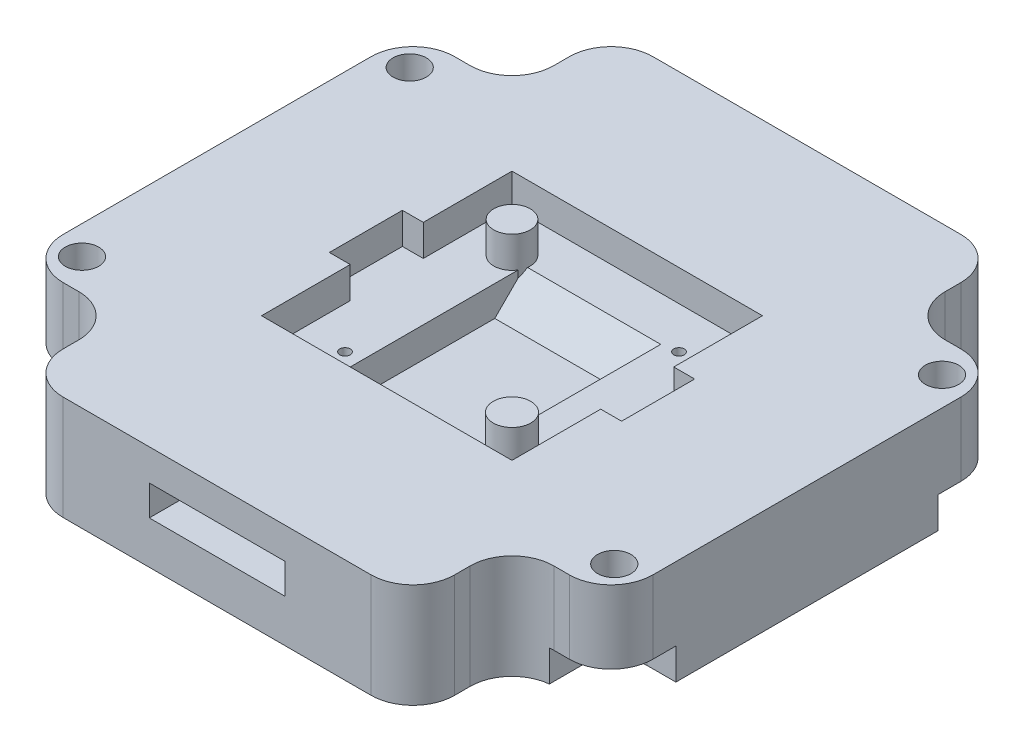
SolidWorks part; units mm, degrees
ref_plane "Ebene vorne" through (0, 0, 0) normal (0, 0, 1) x (1, 0, 0)
ref_plane "Ebene oben" through (0, 0, 0) normal (0, 1, 0) x (1, 0, 0)
ref_plane "Ebene rechts" through (0, 0, 0) normal (1, 0, 0) x (0, 0, -1)
sketch "Skizze1" plane through (0, 0, 0) normal (0, 1, 0) x (1, 0, 0)
  line L0 (18.75, 18.75) -> (28.25, 18.75)
  line L1 (-28.25, 18.75) -> (-18.75, 18.75)
  line L2 (-28.25, 18.75) -> (-28.25, -18.75)
  line L3 (-28.25, -18.75) -> (-18.75, -18.75)
  line L4 (28.25, 18.75) -> (28.25, -18.75)
  line L5 (-28.25, 18.75) -> (28.25, -18.75) construction
  line L6 (-28.25, -18.75) -> (28.25, 18.75) construction
  line L7 (-18.75, -28.25) -> (18.75, -28.25)
  line L8 (-18.75, -28.25) -> (-18.75, -18.75)
  line L9 (-18.75, 28.25) -> (18.75, 28.25)
  line L10 (18.75, -28.25) -> (18.75, -18.75)
  line L11 (-18.75, -28.25) -> (18.75, 28.25) construction
  line L12 (-18.75, 28.25) -> (18.75, -28.25) construction
  line L13 (18.75, 18.75) -> (18.75, 28.25)
  line L14 (18.75, -18.75) -> (28.25, -18.75)
  line L15 (-18.75, 18.75) -> (-18.75, 28.25)
  point P0 (0, 0)
  point P6 (0, 0)
  dimension "D1" = 56.5
  dimension "D2" = 56.5
  dimension "D3" = 37.5
extrude "Aufsatz-Linear austragen1" add sketch "Skizze1" along normal blind 10
sketch "Skizze2" plane through (0, 10, 0) normal (0, 1, 0) x (1, 0, 0)
  line L1 (-12, 12) -> (12, 12)
  line L2 (-12, 12) -> (-12, -12)
  line L3 (-12, -12) -> (12, -12)
  line L4 (12, 12) -> (12, -12)
  line L5 (-12, 12) -> (12, -12) construction
  line L6 (-12, -12) -> (12, 12) construction
  point P0 (0, 0)
  dimension "D1" = 24
extrude "Schnitt-Linear austragen1" cut sketch "Skizze2" against normal blind 3
fillet "Verrundung1" radius 4 12 edges at (-28.25, 5, 18.75) (-18.75, 5, 28.25) (-28.25, 5, -18.75) (-18.75, 5, -28.25) (18.75, 5, -28.25) (28.25, 5, -18.75) (28.25, 5, 18.75) (18.75, 5, 28.25) (18.75, 5, 18.75) (-18.75, 5, 18.75) (-18.75, 5, -18.75) (18.75, 5, -18.75)
sketch "Skizze3" plane through (0, 7, 0) normal (0, 1, 0) x (1, 0, 0)
  line L1 (-8, -8) -> (8, -8) construction
  line L2 (-8, -8) -> (-8, 8) construction
  line L3 (-8, 8) -> (8, 8) construction
  line L4 (8, -8) -> (8, 8) construction
  line L5 (-8, -8) -> (8, 8) construction
  line L6 (-8, 8) -> (8, -8) construction
  circle A0 centre (-8, 8) radius 1.75
  circle A2 centre (8, -8) radius 1.8
  point P0 (0, 0)
  dimension "D2" = 3.5
  dimension "D1" = 16
extrude "Aufsatz-Linear austragen2" add sketch "Skizze3" along normal blind 3
sketch "Skizze4" plane through (0, 10, 0) normal (0, 1, 0) x (1, 0, 0)
  line L0 (0, 0) -> (-50000, 0) construction
  line L1 (12, 3.5) -> (14, 3.5)
  line L2 (12, -12) -> (12, 12) construction
  line L3 (14, 3.5) -> (14, -3.5)
  line L4 (14, -3.5) -> (12, -3.5)
  line L5 (12, -3.5) -> (12, 3.5)
  dimension "D1" = 2
  dimension "D2" = 7
extrude "Schnitt-Linear austragen2" cut sketch "Skizze4" against normal blind 3
mirror "Spiegeln1" about plane through (0, 0, 0) normal (1, 0, 0) of "Schnitt-Linear austragen2"
sketch "Skizze5" plane through (0, 0, 28.25) normal (0, 0, 1) x (1, 0, 0)
  line L0 (0, 0) -> (0, -50000) construction
  line L2 (-14.75, 0) -> (14.75, 0) construction
  line L3 (-6.5, 7) -> (6.5, 7)
  line L4 (-6.5, 7) -> (-6.5, 4.1)
  line L5 (-6.5, 4.1) -> (6.5, 4.1)
  line L6 (6.5, 7) -> (6.5, 4.1)
  line L7 (-6.5, 7) -> (6.5, 4.1) construction
  line L8 (-6.5, 4.1) -> (6.5, 7) construction
  point P3 (0, 5.55)
  dimension "D1" = 2.9
  dimension "D2" = 13
  dimension "D3" = 4.1
extrude "Schnitt-Linear austragen3" cut sketch "Skizze5" against normal blind 32
chamfer "Fase1" distance 4 angle 45 1 edges at (0, 7, -3.75)
hole_wizard "Ø3.2 (3.2) Durchmesser Bohrung1" positions "Skizze8" profile "Skizze9" hole size "Ø3.2" standard "ISO"
sketch "Skizze8" plane through (0, 10, 0) normal (0, 1, 0) x (1, 0, 0)
  line L1 (25.5, 15.7) -> (-25.5, 15.7) construction
  line L2 (25.5, 15.7) -> (25.5, -15.7) construction
  line L3 (25.5, -15.7) -> (-25.5, -15.7) construction
  line L4 (-25.5, 15.7) -> (-25.5, -15.7) construction
  line L5 (25.5, 15.7) -> (-25.5, -15.7) construction
  line L6 (25.5, -15.7) -> (-25.5, 15.7) construction
  point P2 (-25.5, -15.7)
  point P195 (25.5, 15.7)
  point P196 (25.5, -15.7)
  point P197 (-25.5, 15.7)
  dimension "D1" = 51
  dimension "D2" = 31.4
sketch "Skizze9" plane through (-25.5, 10, 15.7) normal (1, 0, 0) x (0, 0, 1)
  line L0 (0, 0) -> (0, 11.9614)
  line L1 (0, 11.9614) -> (1.6, 11)
  line L2 (1.6, 11) -> (1.6, 0)
  line L5 (1.6, 0) -> (0, 0)
  line L10 (0, 11.9614) -> (-1.6, 11) construction
  line L11 (0, -6.35) -> (0, 107.95) construction
  dimension "Bohrerdurchmesser" = 3.2
  dimension "Bohrungstiefe" = 11
  dimension "Spitzenwinkel" = 118
hole_wizard "Ø1.0 (1) Durchmesser Bohrung1" positions "Skizze10" profile "Skizze11" hole size "Ø1.0" standard "ISO"
sketch "Skizze10" plane through (0, 7, 0) normal (0, 1, 0) x (1, 0, 0)
  line L1 (-8, 8) -> (8, 8)
  line L2 (-8, 8) -> (-8, -8)
  line L3 (-8, -8) -> (8, -8)
  line L4 (8, 8) -> (8, -8)
  line L5 (-8, 8) -> (8, -8) construction
  line L6 (-8, -8) -> (8, 8) construction
  point P456 (-8, -8)
  point P457 (8, 8)
sketch "Skizze11" plane through (8, 7, -8) normal (1, 0, 0) x (0, 0, 1)
  line L0 (0, 0) -> (0, 5.3004)
  line L1 (0, 5.3004) -> (0.5, 5)
  line L2 (0.5, 5) -> (0.5, 0)
  line L5 (0.5, 0) -> (0, 0)
  line L10 (0, 5.3004) -> (-0.5, 5) construction
  line L11 (0, -6.35) -> (0, 107.95) construction
  dimension "Bohrerdurchmesser" = 1
  dimension "Bohrungstiefe" = 5
  dimension "Spitzenwinkel" = 118
sketch "Skizze12" plane through (0, 0, 0) normal (0, -1, 0) x (1, 0, 0)
  line L0 (-22.35, 15.7) -> (-22.35, 18.85)
  line L1 (-25.5, 18.85) -> (-22.35, 18.85)
  line L2 (-25.5, 12.55) -> (-28.65, 12.55)
  line L3 (-28.65, 12.55) -> (-28.65, 15.7)
  arc A0 (-25.5, 12.55) -> (-22.35, 15.7) centre (-25.5, 15.7) ccw
  arc A1 (-25.5, 18.85) -> (-28.65, 15.7) centre (-25.5, 15.7) ccw
  dimension "D1" = 6.3
extrude "Schnitt-Linear austragen4" cut sketch "Skizze12" against normal blind 3
mirror "Spiegeln2" about plane through (0, 0, 0) normal (1, 0, 0) of "Schnitt-Linear austragen4"
mirror "Spiegeln3" about plane through (0, 0, 0) normal (0, 0, 1) of "Spiegeln2"
